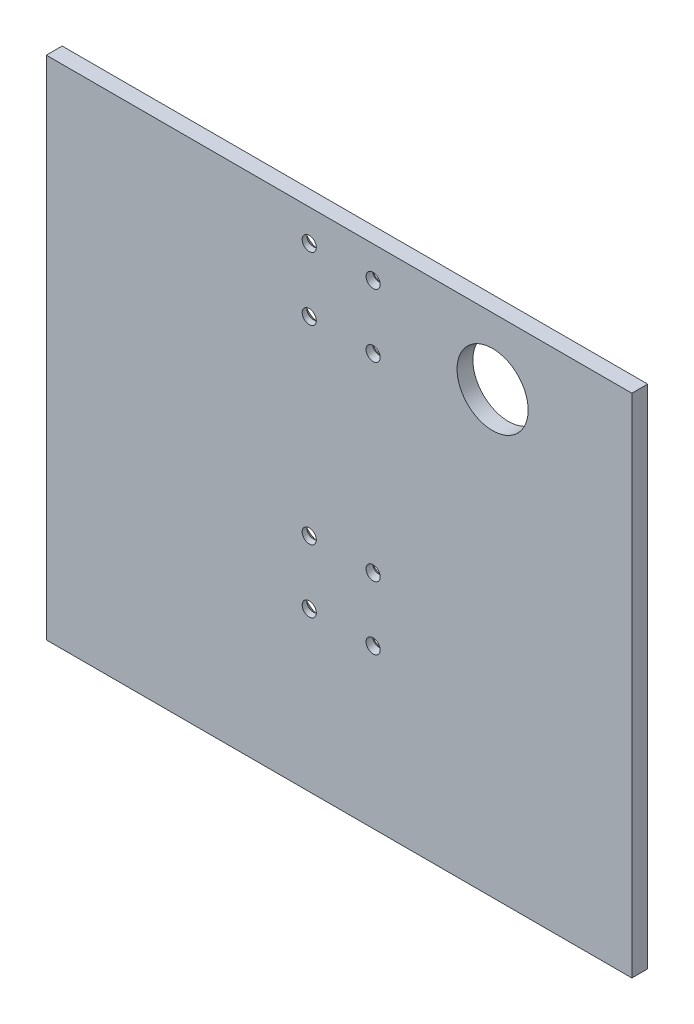
SolidWorks part; units mm, degrees
material "PC High Viscosity"
ref_plane "Front Plane" through (0, 0, 0) normal (0, 0, 1) x (1, 0, 0)
ref_plane "Top Plane" through (0, 0, 0) normal (0, 1, 0) x (1, 0, 0)
ref_plane "Right Plane" through (0, 0, 0) normal (1, 0, 0) x (0, 0, -1)
sketch "Sketch1" plane through (0, 0, 0) normal (0, 0, 1) x (1, 0, 0)
  line L1 (-117.475, -101.6) -> (117.475, -101.6)
  line L2 (-117.475, -101.6) -> (-117.475, 101.6)
  line L3 (-117.475, 101.6) -> (117.475, 101.6)
  line L4 (117.475, -101.6) -> (117.475, 101.6)
  line L5 (-117.475, -101.6) -> (117.475, 101.6) construction
  line L6 (-117.475, 101.6) -> (117.475, -101.6) construction
  point P0 (0, 0)
  dimension "D1" = 234.95
  dimension "D2" = 203.2
extrude "Boss-Extrude1" add sketch "Sketch1" along normal blind 6.35
sketch "Sketch2" plane through (0, 0, 6.35) normal (0, 0, 1) x (1, 0, 0)
  line L0 (117.475, 101.6) -> (-117.475, 101.6) construction
  line L1 (117.475, -101.6) -> (117.475, 101.6) construction
  circle A0 centre (61.595, 74.93) radius 14.2748
  dimension "D3" = 28.5496
  dimension "D1" = 26.67
  dimension "D2" = 55.88
extrude "Cut-Extrude1" cut sketch "Sketch2" against normal through all
hole_wizard "CSK for #10 Flat Head Machine Screw (100)1" positions "Sketch3" profile "Sketch4" countersink size "#10" standard "ANSI Inch" end condition through all
sketch "Sketch3" plane through (292.077, -265.5951, -43.8004) normal (0.1349, 0, 0.9909) x (0.9909, 0, -0.1349)
  point P0 (-308.0419, 227.4951)
  point P2 (-308.0419, 252.8951)
  point P4 (-308.042, 329.0951)
  point P6 (-308.042, 354.4951)
sketch "Sketch4" plane through (-13.1497, -38.1, -2.2498) normal (0, 1, 0) x (-0.9909, 0, 0.1349)
  line L0 (0, 0) -> (0, 26.1406)
  line L1 (0, 26.1406) -> (2.8067, 26.1406)
  line L2 (2.8067, 26.1406) -> (2.8067, 6.0833)
  line L3 (2.8067, 6.0833) -> (8.89, 0)
  line L4 (8.89, 0) -> (0, 0)
  line L5 (-2.8067, 6.0833) -> (-8.89, 0) construction
  line L6 (0, -6.35) -> (0, 107.95) construction
  dimension "Thru Hole Dia." = 5.6134
  dimension "Thru Hole Depth" = 26.1406
  dimension "Near C'Sink Dia." = 17.78
  dimension "Near C'Sink Angle" = 90
hole_wizard "CSK for #10 Flat Head Machine Screw (100)2" positions "Sketch5" profile "Sketch6" countersink size "#10" standard "ANSI Inch" end condition through all
sketch "Sketch5" plane through (292.4196, -265.5951, -41.2836) normal (0.1349, 0, 0.9909) x (0.9909, 0, -0.1349)
  point P0 (-282.6419, 227.4951)
  point P2 (-282.6419, 252.8951)
  point P4 (-282.642, 329.0951)
  point P6 (-282.642, 354.4951)
sketch "Sketch6" plane through (12.3608, -38.1, -3.1591) normal (0, 1, 0) x (-0.9909, 0, 0.1349)
  line L0 (0, 0) -> (0, 23.6006)
  line L1 (0, 23.6006) -> (2.8067, 23.6006)
  line L2 (2.8067, 23.6006) -> (2.8067, 6.0833)
  line L3 (2.8067, 6.0833) -> (8.89, 0)
  line L4 (8.89, 0) -> (0, 0)
  line L5 (-2.8067, 6.0833) -> (-8.89, 0) construction
  line L6 (0, -6.35) -> (0, 107.95) construction
  dimension "Thru Hole Dia." = 5.6134
  dimension "Thru Hole Depth" = 23.6006
  dimension "Near C'Sink Dia." = 17.78
  dimension "Near C'Sink Angle" = 90
